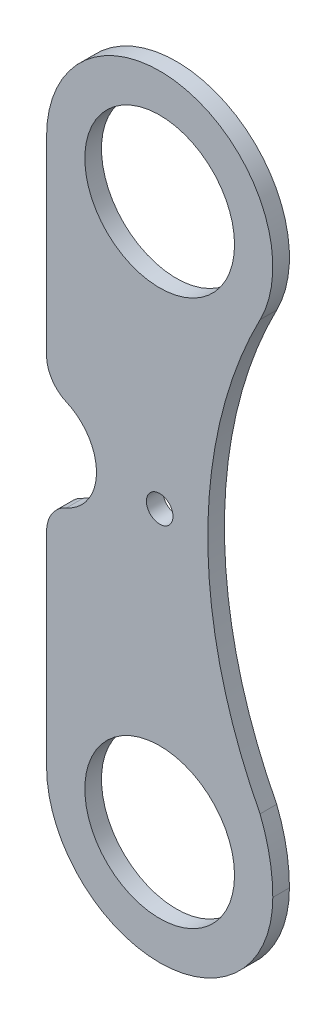
SolidWorks part; units mm, degrees
material "6061 Alloy"
ref_plane "Front Plane" through (0, 0, 0) normal (0, 0, 1) x (1, 0, 0)
ref_plane "Top Plane" through (0, 0, 0) normal (0, 1, 0) x (1, 0, 0)
ref_plane "Right Plane" through (0, 0, 0) normal (1, 0, 0) x (0, 0, -1)
sketch "Sketch1" plane through (0, 0, 0) normal (0, 0, 1) x (1, 0, 0)
  line L0 (0, 0) -> (0, -101.6) construction
  line L1 (21.59, -120.5575) -> (-21.59, -120.5575) construction
  line L2 (-8.89, 25.4) -> (8.89, 25.4)
  line L3 (-21.59, 12.7) -> (-21.59, -117.7751)
  line L5 (21.59, 12.7) -> (21.59, -117.7751)
  line L9 (-23.3829, -122.6853) -> (-33.2033, -134.3394)
  line L10 (-36.322, 25.4) -> (20.828, 25.4) construction
  line L11 (-36.322, 25.4) -> (-36.322, -203.2) construction
  line L12 (-36.322, -203.2) -> (20.828, -203.2) construction
  line L13 (20.828, 25.4) -> (20.828, -203.2) construction
  line L15 (-7.9527, -155.6168) -> (19.7971, -122.6853)
  line L16 (-32.4392, -143.2871) -> (-16.9004, -156.3809)
  circle A0 centre (0, 0) radius 38.1 construction
  circle A1 centre (0, -101.6) radius 38.1 construction
  circle A2 centre (0, 0) radius 14.2875
  circle A3 centre (0, -101.6) radius 14.2875
  arc A6 (8.89, 25.4) -> (21.59, 12.7) centre (8.89, 12.7) cw
  arc A7 (-8.89, 25.4) -> (-21.59, 12.7) centre (-8.89, 12.7) ccw
  circle A10 centre (-18.5321, -142.5501) radius 2.54
  arc A13 (-23.3829, -122.6853) -> (-21.59, -117.7751) centre (-29.21, -117.7751) ccw
  arc A14 (19.7971, -122.6853) -> (21.59, -117.7751) centre (13.97, -117.7751) ccw
  arc A15 (-16.9004, -156.3809) -> (-7.9527, -155.6168) centre (-12.8086, -151.525) ccw
  arc A16 (-33.2033, -134.3394) -> (-32.4392, -143.2871) centre (-28.3474, -138.4312) ccw
  circle A17 centre (0, -50.8) radius 2.54
  point P13 (-192.705, 39.2708)
  point P20 (21.59, 25.4)
  point P23 (-21.59, 25.4)
  point P31 (-36.322, -138.0404)
  dimension "D2" = 76.2
  dimension "D3" = 76.2
  dimension "D4" = 28.575
  dimension "D5" = 28.575
  dimension "D10" = 228.6
  dimension "D11" = 36.322
  dimension "D13" = 5.08
  dimension "D19" = 6.35
  dimension "D20" = 7.62
  dimension "D21" = 12.7
  dimension "D22" = 5.08
  dimension "D1" = 101.6
  dimension "D6" = 43.18
  dimension "D7" = 21.59
  dimension "D8" = 25.4
  dimension "D9" = 57.15
  dimension "D12" = 25.4
  dimension "D14" = 33.02
  dimension "D15" = 16.51
  dimension "D16" = 21.59
  dimension "D17" = 9.525
  dimension "D18" = 18.9575
extrude "Boss-Extrude1" add sketch "Sketch1" along normal blind 3.175
sketch "Sketch2" plane through (0, 0, 0) normal (0, 0, 1) x (1, 0, 0)
  line L0 (-21.59, -41.275) -> (-21.59, -60.325)
  line L1 (0, 0) -> (0, -101.6) construction
  line L4 (21.59, -117.7751) -> (21.59, 12.7) construction
  line L5 (-21.59, -50.8) -> (97.79, -50.8) construction
  line L6 (-21.59, 12.7) -> (-21.59, -117.7751) construction
  line L7 (0, 0) -> (-39.9512, 0) construction
  line L9 (16.51, -115.5122) -> (-17.5013, -155.8745)
  line L10 (-32.4392, -143.2871) -> (-16.9004, -156.3809) construction
  line L11 (-7.9527, -155.6168) -> (19.7971, -122.6853) construction
  line L13 (27.94, -121.6567) -> (-7.6203, -163.8572)
  line L14 (-7.6203, -163.8572) -> (-17.5013, -155.8745)
  line L15 (27.94, -121.6567) -> (27.94, 0)
  line L16 (27.94, 0) -> (21.59, 0)
  arc A1 (19.1591, -91.6472) -> (19.1591, -9.9528) centre (97.79, -50.8) cw
  arc A2 (-21.59, -60.325) -> (-21.59, -41.275) centre (-21.59, -50.8) ccw
  arc A3 (21.59, 0) -> (19.1591, -9.9528) centre (0, 0) cw
  arc A4 (21.59, -101.6) -> (19.1591, -91.6472) centre (0, -101.6) ccw
  arc A5 (21.59, -101.6) -> (16.51, -115.5122) centre (0, -101.6) cw
  dimension "D2" = 12.7
  dimension "D3" = 50.8
  dimension "D4" = 6.35
  dimension "D1" = 76.2
  dimension "D5" = 19.05
extrude "Cut-Extrude1" cut sketch "Sketch2" along normal through all contours A1 A3 L16 L15 L13 L14 L9 A5 A4 | L0 A2
sketch "Sketch3" plane through (0, 0, 3.175) normal (0, 0, 1) x (1, 0, 0)
  line L0 (-27.3514, -127.3948) -> (-36.0255, -137.6886)
  line L3 (-27.3514, -127.3948) -> (-7.5576, -144.074)
  line L4 (-23.3829, -122.6853) -> (-33.2033, -134.3394) construction
  line L5 (16.51, -115.5122) -> (-17.5013, -155.8745) construction
  line L7 (-35.4064, -144.9387) -> (-24.4031, -154.2106)
  line L8 (-23.3829, -122.6853) -> (-33.2033, -134.3394) construction
  line L9 (-7.5576, -144.074) -> (-15.4554, -153.4465)
  line L10 (-32.4392, -143.2871) -> (-17.5013, -155.8745) construction
  circle A2 centre (-18.5321, -142.5501) radius 2.54
  circle A3 centre (-18.5321, -142.5501) radius 2.54 construction
  arc A5 (-36.0255, -137.6886) -> (-35.4064, -144.9387) centre (-32.0909, -141.0041) ccw
  arc A6 (-24.4031, -154.2106) -> (-15.4554, -153.4465) centre (-20.3113, -149.3547) ccw
  dimension "D2" = 6.35
  dimension "D3" = 5.1453
  dimension "D1" = 3.175
fillet "Fillet3" radius 6.35 2 edges at (-21.59, -41.275, 1.5875) (-21.59, -60.325, 1.5875)
extrude "Boss-Extrude3" add sketch "Sketch3" against normal blind 3.175
sketch "Sketch6" plane through (0, 0, 3.175) normal (0, 0, 1) x (1, 0, 0)
  line L0 (-35.4064, -144.9387) -> (-63.6204, -121.1641)
  line L1 (-63.6204, -121.1641) -> (-51.345, -106.5965)
  line L2 (-51.345, -106.5965) -> (-27.0656, -127.0555)
  line L4 (-35.4064, -144.9387) -> (-24.4031, -154.2106) construction
  line L5 (-23.3829, -122.6853) -> (-36.0255, -137.6886) construction
  line L6 (-35.4064, -144.9387) -> (-27.0656, -127.0555)
  circle A0 centre (-52.6268, -117.9721) radius 2.54
  dimension "D4" = 5.08
  dimension "D1" = 31.75
  dimension "D2" = 9.525
  dimension "1" = 19.05
  dimension "D3" = 6.35
extrude "Boss-Extrude4" add sketch "Sketch6" against normal blind 3.175
fillet "Fillet2" radius 6.35 3 edges at (-63.6204, -121.1641, 1.5875) (-51.345, -106.5965, 1.5875) (-27.0656, -127.0555, 1.5875)
sketch "Sketch7" plane through (0, 0, 3.175) normal (0, 0, 1) x (1, 0, 0)
  line L0 (-21.59, 12.7) -> (-21.59, -36.2503) construction
  line L1 (21.59, 0) -> (21.59, 12.7) construction
  line L2 (-21.59, 0) -> (21.59, 0) construction
  line L3 (-21.59, 0) -> (-21.59, 31.75)
  line L4 (-21.59, 31.75) -> (21.59, 31.75)
  line L5 (21.59, 31.75) -> (21.59, 0)
  line L6 (8.89, 25.4) -> (-8.89, 25.4) construction
  arc A0 (-21.59, 0) -> (21.59, 0) centre (0, 0) cw
  dimension "D1" = 6.35
extrude "Cut-Extrude2" cut sketch "Sketch7" against normal through all
sketch "Sketch10" plane through (0, 0, 3.175) normal (0, 0, 1) x (1, 0, 0)
  line L0 (16.51, -115.5122) -> (-17.5013, -155.8745) construction
  line L1 (-18.1519, -155.3263) -> (-17.3615, -157.512)
  line L2 (-17.3615, -157.512) -> (-14.3757, -156.4323)
  line L3 (-14.3757, -156.4323) -> (-15.4554, -153.4465)
  line L5 (-18.1519, -155.3263) -> (-17.5013, -155.8745) construction
  circle A0 centre (-20.3113, -149.3547) radius 6.35 construction
  arc A1 (-24.4031, -154.2106) -> (-18.1519, -155.3263) centre (-20.3113, -149.3547) ccw construction
  arc A2 (-18.1519, -155.3263) -> (-15.4554, -153.4465) centre (-20.3113, -149.3547) ccw
  dimension "D1" = 3.175
  dimension "D2" = 30
extrude "Cut-Extrude3" cut sketch "Sketch10" against normal through all
sketch "Sketch12" plane through (0, 0, 3.175) normal (0, 0, 1) x (1, 0, 0)
  line L0 (-21.59, -65.3497) -> (-21.59, -117.7751) construction
  line L1 (-21.59, -101.6) -> (-72.39, -101.6)
  line L2 (-72.39, -101.6) -> (-72.39, -165.1)
  line L3 (-72.39, -165.1) -> (16.51, -165.1)
  line L4 (16.51, -165.1) -> (16.51, -115.5122)
  arc A2 (16.51, -115.5122) -> (-21.59, -101.6) centre (0, -101.6) cw
  dimension "D1" = 63.5
  dimension "D2" = 88.9
extrude "Cut-Extrude4" cut sketch "Sketch12" against normal through all
sketch "Sketch13" plane through (0, 0, 3.175) normal (0, 0, 1) x (1, 0, 0)
  line L0 (-21.59, -101.6) -> (-21.59, -104.2391)
  line L1 (21.59, -101.6) -> (21.59, -104.2391)
  line L2 (-21.59, -101.6) -> (-7.35, -118.3664)
  line L3 (-7.35, -118.3664) -> (6.6629, -118.3664)
  line L4 (6.6629, -118.3664) -> (21.59, -101.6)
  arc A0 (-21.59, -104.2391) -> (21.59, -104.2391) centre (0, -104.2391) ccw
  arc A1 (-21.59, -101.6) -> (19.1591, -91.6472) centre (0, -101.6) ccw construction
  dimension "D1" = 2.6391
extrude "Boss-Extrude7" add sketch "Sketch13" against normal through all contours A0 L1 L4 L3 L2 L0
sketch "Sketch14" plane through (0, 0, 3.175) normal (0, 0, 1) x (1, 0, 0)
  circle A0 centre (0, -101.6) radius 14.2875
  circle A1 centre (0, -101.6) radius 14.2875 construction
extrude "Boss-Extrude8" add sketch "Sketch14" against normal through all
sketch "Sketch15" plane through (0, 0, 3.175) normal (0, 0, 1) x (1, 0, 0)
  circle A0 centre (0, -104.2391) radius 14.2875
  arc A1 (-21.59, -104.2391) -> (21.59, -104.2391) centre (0, -104.2391) ccw construction
  dimension "D1" = 28.575
extrude "Cut-Extrude5" cut sketch "Sketch15" against normal through all
sketch "Sketch16" plane through (0, 0, 3.175) normal (0, 0, 1) x (1, 0, 0)
  line L0 (21.59, -104.2391) -> (21.59, -94.3525) construction
  line L1 (19.1591, -91.6472) -> (21.59, -91.6472)
  line L2 (21.59, -91.6472) -> (21.59, -104.2391)
  arc A0 (19.1591, -91.6472) -> (21.59, -104.2391) centre (-12.2375, -104.2391) cw
extrude "Cut-Extrude6" cut sketch "Sketch16" against normal through all
